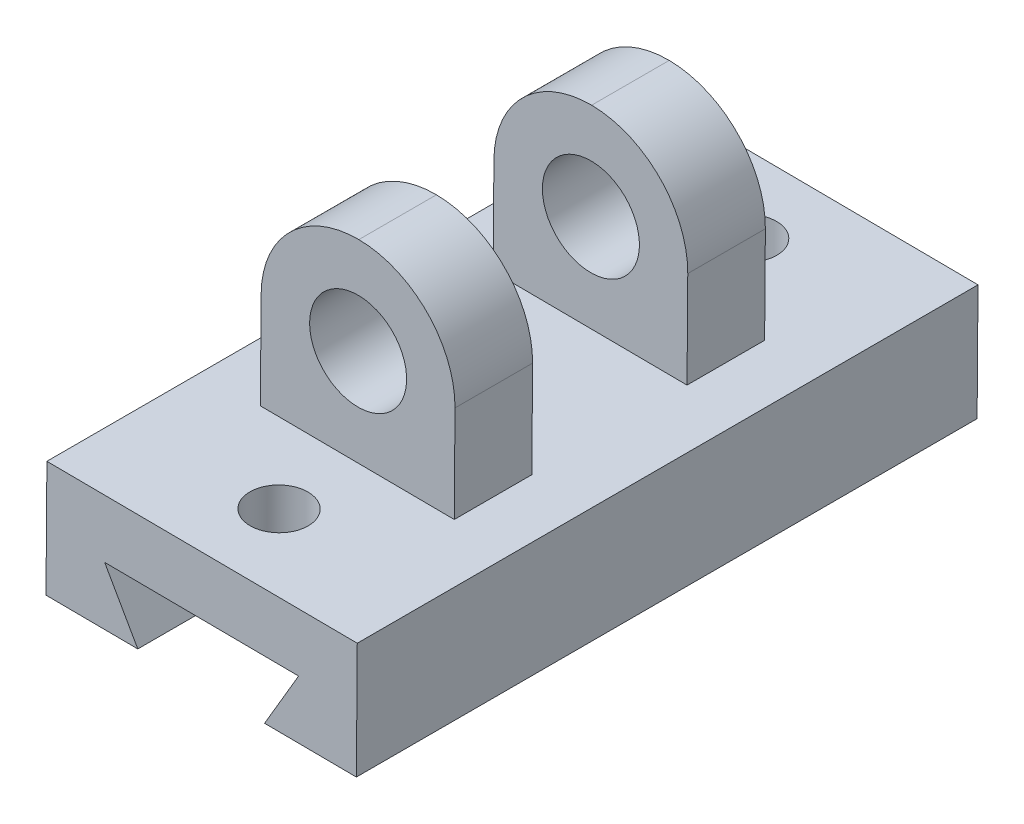
SolidWorks part; units mm, degrees
ref_plane "Front Plane" through (0, 0, 0) normal (0, 0, 1) x (1, 0, 0)
ref_plane "Top Plane" through (0, 0, 0) normal (0, 1, 0) x (1, 0, 0)
ref_plane "Right Plane" through (0, 0, 0) normal (1, 0, 0) x (0, 0, -1)
sketch "Sketch9" plane through (0, 0, 0) normal (0, 0, 1) x (1, 0, 0)
  line L0 (-46.1273, 8.0111) -> (33.8727, 7.4)
  line L1 (-46.3564, -21.9881) -> (-22.6968, -22.1688)
  line L2 (-31.2423, -7.1031) -> (18.7586, -7.485)
  line L3 (-46.1273, 8.0111) -> (-46.3564, -21.9881)
  line L4 (-46.2418, -6.9885) -> (33.7582, -7.5995) construction
  line L5 (-31.2423, -7.1031) -> (-22.6968, -22.1688)
  line L6 (9.984, -22.4184) -> (33.6436, -22.5991)
  line L7 (18.7586, -7.485) -> (9.984, -22.4184)
  line L8 (33.8727, 7.4) -> (33.6436, -22.5991)
  line L9 (-46.3564, -21.9881) -> (33.6436, -22.5991) construction
extrude "Boss-Extrude2" add sketch "Sketch9" against normal blind 160
sketch "Sketch10" plane through (0.0585, 7.6583, 0) normal (0.0076, 1, 0) x (1, -0.0076, 0)
  line L4 (-46.1871, 0) -> (33.8152, 0)
  line L5 (-46.1871, 80) -> (33.8152, 80)
  line L6 (-46.1871, 160) -> (-46.1871, 0) construction
  line L7 (33.8152, 160) -> (33.8152, 0) construction
  circle A0 centre (-5.9525, 19.6024) radius 7.5
  circle A1 centre (-5.9525, 140.3976) radius 7.5
extrude "Cut-Extrude3" cut sketch "Sketch10" against normal blind 37 contours A1 | A0
sketch "Sketch15" plane through (0.0585, 7.6583, 0) normal (0.0076, 1, 0) x (1, -0.0076, 0)
  line L0 (33.8152, 0) -> (-46.1871, 0) construction
  line L1 (-31.1578, 60) -> (18.8152, 60)
  line L2 (-31.1578, 60) -> (-31.1578, 40)
  line L3 (-31.1578, 40) -> (18.8152, 40)
  line L4 (18.8152, 60) -> (18.8152, 40)
  line L5 (33.8152, 160) -> (33.8152, 0) construction
  line L8 (18.8152, 100) -> (18.8152, 120)
  line L9 (-31.1578, 120) -> (18.8152, 120)
  line L10 (-31.1578, 100) -> (-31.1578, 120)
  line L11 (-31.1578, 100) -> (18.8152, 100)
  dimension "D1" = 40
  dimension "D2" = 15
extrude "Boss-Extrude3" add sketch "Sketch15" along normal blind 50
fillet "Fillet8" radius 25 1 edges at (-30.7165, 57.8948, -50)
fillet "Fillet9" radius 25 1 edges at (19.2551, 57.5131, -50)
fillet "Fillet10" radius 25 1 edges at (-30.7165, 57.8948, -110)
fillet "Fillet11" radius 25 1 edges at (19.2551, 57.5131, -110)
sketch "Sketch20" plane through (0, 0, -120) normal (0, 0, -1) x (-1, 0, 0)
  circle A0 centre (5.9082, 32.7046) radius 12.5
extrude "Cut-Extrude16" cut sketch "Sketch20" against normal blind 120
